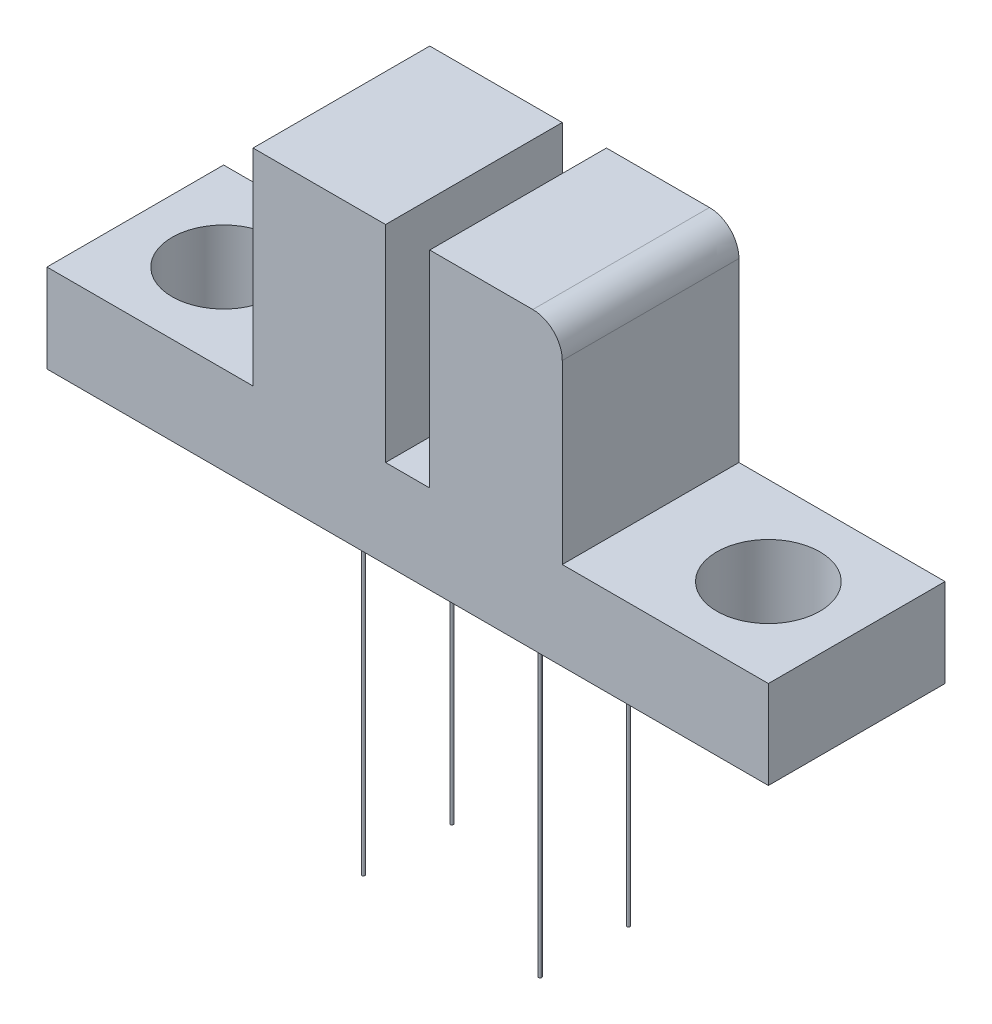
SolidWorks part; units mm, degrees
ref_plane "Alzado" through (0, 0, 0) normal (0, 0, 1) x (1, 0, 0)
ref_plane "Planta" through (0, 0, 0) normal (0, 1, 0) x (1, 0, 0)
ref_plane "Vista lateral" through (0, 0, 0) normal (1, 0, 0) x (0, 0, -1)
sketch "Croquis1" plane through (0, 0, 0) normal (0, 1, 0) x (1, 0, 0)
  line L0 (-12.25, 0) -> (-12.25, 38.8174) construction
  line L1 (0, 0) -> (-24.5, 0)
  line L2 (0, 0) -> (0, -6)
  line L3 (0, -6) -> (-24.5, -6)
  line L4 (-24.5, 0) -> (-24.5, -6)
  circle A0 centre (-21.5, -3) radius 1.75
  circle A1 centre (-3, -3) radius 1.75
  point P10 (-24.5, -3)
  dimension "D3" = 3.5
  dimension "D4" = 3
  dimension "D1" = 6
  dimension "D2" = 24.5
extrude "Saliente-Extruir1" add sketch "Croquis1" along normal blind 3
sketch "Croquis2" plane through (0, 3, 0) normal (0, 1, 0) x (1, 0, 0)
  line L0 (0, 0) -> (-24.5, 0) construction
  line L1 (-17.5, 0) -> (-13, 0)
  line L2 (-17.5, 0) -> (-17.5, -6)
  line L3 (-17.5, -6) -> (-13, -6)
  line L4 (-13, 0) -> (-13, -6)
  line L5 (-24.5, -6) -> (0, -6) construction
  line L6 (-12.25, -6) -> (-12.25, -8.8549) construction
  line L7 (-24.5, 0) -> (-24.5, -6) construction
  line L8 (-7, -6) -> (-11.5, -6)
  line L9 (-11.5, 0) -> (-11.5, -6)
  line L10 (-7, 0) -> (-11.5, 0)
  line L11 (-7, 0) -> (-7, -6)
  dimension "D1" = 4.5
  dimension "D2" = 7
extrude "Saliente-Extruir2" add sketch "Croquis2" along normal blind 7
fillet "Redondeo1" radius 1 1 edges at (-7, 10, 3) conic radius 1
sketch "Croquis3" plane through (0, 0, 0) normal (0, -1, 0) x (1, 0, 0)
  line L2 (-13, 0) -> (-13, 6) construction
  line L3 (-13, 6) -> (-11.5, 6) construction
  line L4 (-17.5, 0) -> (-17.5, 6) construction
  line L5 (-17.5, 6) -> (-13, 6) construction
  line L7 (-13, 0) -> (-17.5, 0) construction
  line L10 (-13, 0) -> (-13, 6) construction
  line L11 (-13, 6) -> (-11.5, 6) construction
  line L12 (-17.5, 0) -> (-17.5, 6) construction
  line L13 (-17.5, 6) -> (-13, 6) construction
  line L15 (-13, 0) -> (-17.5, 0) construction
  line L16 (-12.25, 6) -> (-12.25, 7.3947) construction
  line L21 (-15.25, 6) -> (-15.25, 4.5) construction
  line L22 (-13, 3) -> (-13.4415, 3) construction
  circle A0 centre (-15.25, 4.5) radius 0.05
  circle A1 centre (-15.25, 1.5) radius 0.05
  circle A2 centre (-9.25, 4.5) radius 0.05
  circle A3 centre (-9.25, 1.5) radius 0.05
  dimension "D2" = 0.1
  dimension "D1" = 1.5
extrude "Saliente-Extruir3" add sketch "Croquis3" along normal blind 11
sketch "Croquis4" plane through (0, 0, 0) normal (0, -1, 0) x (1, 0, 0)
  line L0 (-21.5, 3) -> (-3, 3) construction
  dimension "D1" = 18.5
